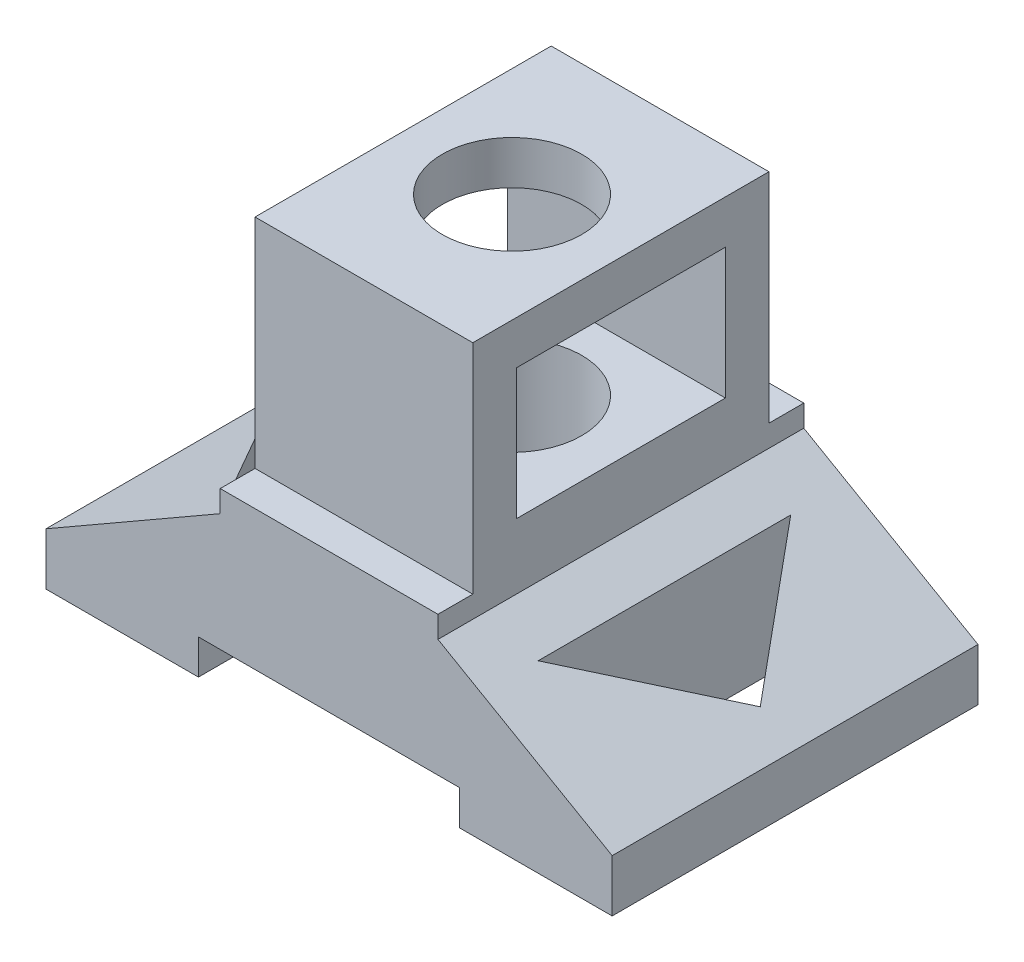
SolidWorks part; units mm, degrees
ref_plane "Front Plane" through (0, 0, 0) normal (0, 0, 1) x (1, 0, 0)
ref_plane "Top Plane" through (0, 0, 0) normal (0, 1, 0) x (1, 0, 0)
ref_plane "Right Plane" through (0, 0, 0) normal (1, 0, 0) x (0, 0, -1)
sketch "Sketch1" plane through (0, 0, 0) normal (0, 0, 1) x (1, 0, 0)
  line L0 (0, 0) -> (0, 8) construction
  line L1 (-30, 8) -> (30, 8)
  line L2 (30, 8) -> (30, 0)
  line L3 (30, 0) -> (65, 0)
  line L4 (65, 0) -> (65, 12)
  line L5 (65, 12) -> (25, 35)
  line L6 (25, 35) -> (25, 90)
  line L7 (25, 90) -> (-25, 90)
  line L8 (0, 90) -> (0, 8) construction
  line L9 (-25, 35) -> (-25, 90)
  line L10 (-65, 12) -> (-25, 35)
  line L11 (-65, 0) -> (-65, 12)
  line L12 (-30, 0) -> (-65, 0)
  line L13 (-30, 8) -> (-30, 0)
  line L14 (-25, 40) -> (25, 40)
  dimension "D1" = 60
  dimension "D2" = 130
  dimension "D3" = 8
  dimension "D4" = 12
  dimension "D5" = 90
  dimension "D6" = 50
  dimension "D7" = 40
  dimension "D8" = 35
extrude "Boss-Extrude1" add sketch "Sketch1" along normal blind 42 and the other way blind 42 contours L14 L9 L10 L11 L12 L13 L1 L2 L3 L4 L5 L6 region at (0, 18.2157, 0)
extrude "Boss-Extrude2" add sketch "Sketch1<3>" along normal blind 34 and the other way blind 34 contours L9 L14 L6 L7 region at (0, 65, 0)
sketch "Sketch1<3>" plane through (0, 0, 0) normal (0, 0, 1) x (1, 0, 0) same geometry as "Sketch1"
sketch "Sketch2" plane through (25, 0, 0) normal (1, 0, 0) x (0, 0, -1)
  line L0 (-24, 80) -> (24, 80)
  line L1 (-24, 80) -> (-24, 50)
  line L2 (24, 80) -> (24, 50)
  line L3 (-24, 50) -> (24, 50)
  line L4 (-24, 80) -> (24, 50) construction
  line L5 (24, 80) -> (-24, 50) construction
  line L6 (0, 90) -> (0, 35) construction
  line L7 (34, 90) -> (-34, 90) construction
  line L8 (42, 35) -> (-42, 35) construction
  line L9 (34, 40) -> (34, 90) construction
  point P1 (0, 65)
  point P11 (0, 0)
  point P14 (34, 65)
  dimension "D1" = 48
  dimension "D2" = 30
extrude "Cut-Extrude1" cut sketch "Sketch2" against normal through all
sketch "Sketch3" plane through (0, 0, 0) normal (0, -1, 0) x (1, 0, 0)
  line L0 (-35, 29) -> (-57, 0)
  line L1 (-57, 0) -> (-35, -29)
  line L2 (-35, -29) -> (-35, 29)
  line L3 (0, 0) -> (0, 32.3722) construction
  line L4 (35, -29) -> (35, 29)
  line L5 (57, 0) -> (35, -29)
  line L6 (35, 29) -> (57, 0)
  circle A0 centre (0, 0) radius 16
  point P7 (-35, 0)
  dimension "D4" = 32
  dimension "D1" = 114
  dimension "D2" = 70
  dimension "D3" = 58
extrude "Cut-Extrude2" cut sketch "Sketch3" against normal through all
